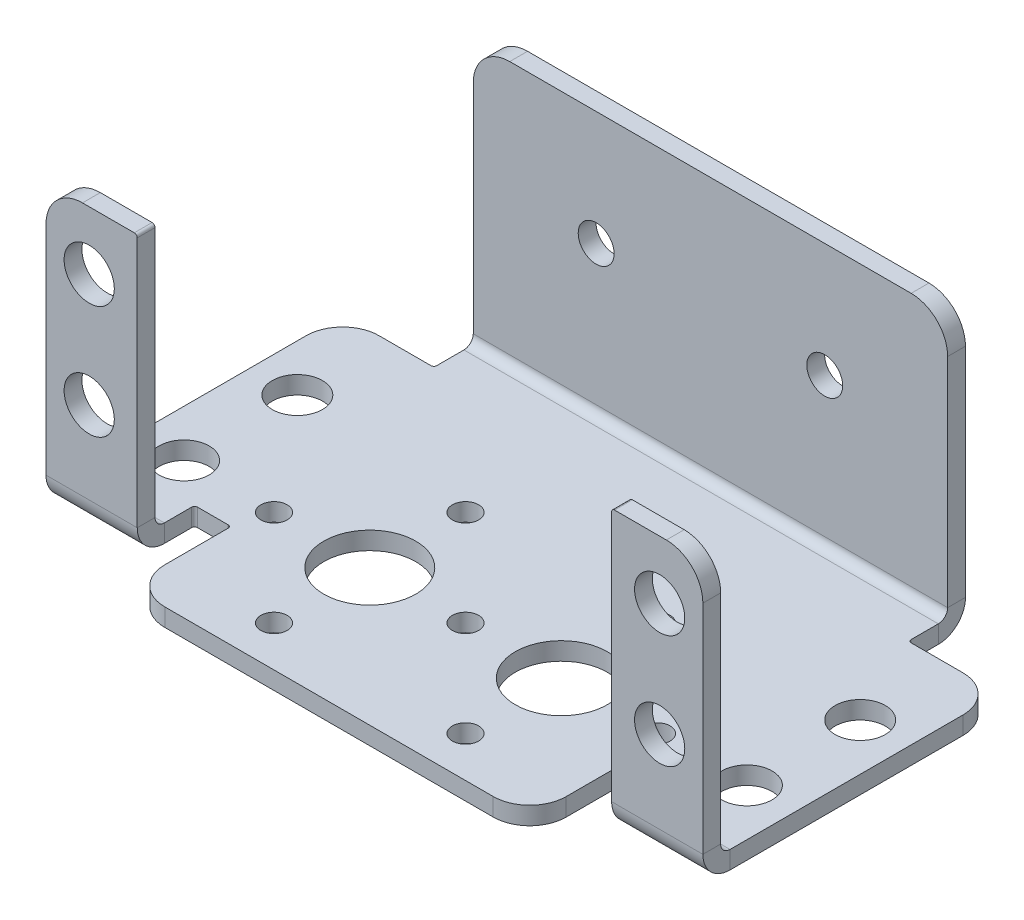
SolidWorks part; units mm, degrees
note: The reader was unsure of these and kept them because the rebuilt part matched: flange length of "Edge-Flange1", "Edge-Flange2".
material "5052-H32"
ref_plane "Front Plane" through (0, 0, 0) normal (0, 0, 1) x (1, 0, 0)
ref_plane "Top Plane" through (0, 0, 0) normal (0, 1, 0) x (1, 0, 0)
ref_plane "Right Plane" through (0, 0, 0) normal (1, 0, 0) x (0, 0, -1)
sketch "Sketch1" plane through (0, 0, 0) normal (0, 1, 0) x (1, 0, 0)
  line L0 (0, 0) -> (0, -11.8745) construction
  line L1 (0, 0) -> (0, 21.3106) construction
  line L2 (-17.4625, -11.8745) -> (17.4625, -11.8745)
  line L3 (17.4625, -11.8745) -> (17.4625, -2.9337)
  line L4 (-17.4625, -11.8745) -> (-17.4625, -2.9337)
  line L5 (17.4625, -2.9337) -> (20.6375, -2.9337)
  line L6 (-17.4625, -2.9337) -> (-20.6375, -2.9337)
  line L7 (20.6375, -2.9337) -> (20.6375, -6.3754)
  line L8 (-20.6375, -2.9337) -> (-20.6375, -6.3754)
  line L9 (20.6375, -6.3754) -> (28.575, -6.3754)
  line L10 (-20.6375, -6.3754) -> (-28.575, -6.3754)
  line L11 (-28.575, -6.3754) -> (-28.575, 17.8816)
  line L12 (28.575, -6.3754) -> (28.575, 17.8816)
  line L13 (-28.575, 17.8816) -> (-20.6375, 17.8816)
  line L14 (28.575, 17.8816) -> (20.6375, 17.8816)
  line L15 (-20.6375, 21.3106) -> (20.6375, 21.3106)
  line L16 (-20.6375, 17.8816) -> (-20.6375, 21.3106)
  line L17 (20.6375, 17.8816) -> (20.6375, 21.3106)
  dimension "D1" = 11.8745
  dimension "D2" = 21.3106
  dimension "D3" = 34.925
  dimension "D4" = 8.9408
  dimension "D5" = 41.275
  dimension "D6" = 7.9375
  dimension "D7" = 7.9375
  dimension "D8" = 3.429
  dimension "D9" = 24.257
sheet metal parameters "Sheet-Metal1" thickness 1.5494 parameters "D1"=0.8128
base flange "Base-Flange1" sketch "Sketch1" thickness 1.5494 reverse thickness direction yes parameters "D1"=0.8128
edge flange "Edge-Flange1" sketch "Sketch5" flange angle 90 flange length 24.4602 flange position material outside bend radius 0.8128 thickness 1.5494 relief rectangular parameters "D6"=10
sketch "Sketch5" plane through (0, 1.5494, -21.3106) normal (0, 0, -1) x (-1, 0, 0)
  line L0 (-20.6375, 0) -> (20.6375, 0) construction
  line L1 (-20.6375, 0) -> (20.6375, 0)
  line L2 (-20.6375, 0) -> (-20.6375, 22.9108)
  line L3 (-20.6375, 22.9108) -> (20.6375, 22.9108)
  line L4 (20.6375, 22.9108) -> (20.6375, 0)
bend "EdgeBend1" bend radius 0.8128 bend angle 90 parameters "D5"=1
edge flange "Edge-Flange2" sketch "Sketch10" flange profiles "Sketch10", "Sketch11" flange angle 90 flange length 24.4602 flange position material outside bend radius 0.8128 thickness 1.5494 relief rectangular parameters "D6"=10, "D8"=0.508
sketch "Sketch10" plane through (0, 1.5494, 6.3754) normal (0, 0, 1) x (1, 0, 0)
  line L2 (-28.575, 0) -> (-28.575, 22.9108)
  line L3 (-28.575, 22.9108) -> (-20.6375, 22.9108)
  line L4 (-20.6375, 22.9108) -> (-20.6375, 0)
  line L5 (-28.575, 0) -> (-20.6375, 0) construction
  line L6 (-28.575, 0) -> (-20.6375, 0)
sketch "Sketch11" plane through (0, 1.5494, 6.3754) normal (0, 0, 1) x (1, 0, 0)
  line L0 (20.6375, 0) -> (28.575, 0) construction
  line L1 (20.6375, 0) -> (28.575, 0)
  line L2 (20.6375, 0) -> (20.6375, 22.9108)
  line L3 (20.6375, 22.9108) -> (28.575, 22.9108)
  line L4 (28.575, 22.9108) -> (28.575, 0)
bend "EdgeBend2" bend radius 0.8128 bend angle 90 parameters "D5"=2
bend "EdgeBend3" bend radius 0.8128 bend angle 90 parameters "D5"=3
sketch "Sketch13" plane through (0, 1.5494, 0) normal (0, 1, 0) x (1, 0, 0)
  line L0 (0, 0) -> (8.3312, 0) construction
  line L1 (8.3312, 0) -> (16.6624, 0) construction
  line L2 (0, 0) -> (-8.3312, 0) construction
  line L3 (-8.3312, 0) -> (-16.6624, 0) construction
  line L4 (8.3312, 0) -> (8.3312, 8.3312) construction
  line L5 (-8.3312, 0) -> (-8.3312, 8.3312) construction
  line L6 (8.3312, 0) -> (8.3312, -8.3312) construction
  line L7 (-8.3312, 0) -> (-8.3312, -8.3312) construction
  line L8 (-16.6624, 0) -> (-24.4856, 0) construction
  line L9 (8.3312, -9.4742) -> (8.3312, -11.8745) construction
  line L10 (-24.4856, 9.8552) -> (-24.4856, 0) construction
  line L11 (16.6624, 0) -> (24.4856, 0) construction
  line L12 (-17.4625, -11.8745) -> (17.4625, -11.8745) construction
  line L13 (24.4856, 9.8552) -> (24.4856, 0) construction
  line L14 (26.67, 0) -> (28.575, 0) construction
  line L15 (28.575, -5.5626) -> (28.575, 17.8816) construction
  circle A0 centre (0, 0) radius 1.143
  circle A1 centre (8.3312, 8.3312) radius 1.143
  circle A2 centre (8.3312, -8.3312) radius 1.143
  circle A3 centre (16.6624, 0) radius 1.143
  circle A4 centre (-8.3312, 8.3312) radius 1.143
  circle A5 centre (-8.3312, -8.3312) radius 1.143
  circle A6 centre (-16.6624, 0) radius 1.143
  circle A7 centre (-8.3312, 0) radius 4.0005
  circle A8 centre (8.3312, 0) radius 4.0005
  circle A9 centre (-24.4856, 9.8552) radius 2.1844
  circle A10 centre (-24.4856, 0) radius 2.1844
  circle A11 centre (24.4856, 9.8552) radius 2.1844
  circle A12 centre (24.4856, 0) radius 2.1844
  dimension "D2" = 2.286
  dimension "D3" = 8.001
  dimension "D6" = 4.3688
  dimension "D1" = 8.3312
  dimension "D4" = 7.8232
  dimension "D5" = 9.8552
extrude "Extrude2" cut sketch "Sketch13" against normal blind 1.5494
sketch "Sketch14" plane through (0, 0, 7.9248) normal (0, 0, 1) x (1, 0, 0)
  line L0 (0, 0) -> (0, 19.3802) construction
  line L1 (-24.8158, 21.5646) -> (-24.8158, 24.4602) construction
  line L2 (-24.8158, 19.3802) -> (-24.8158, 9.525) construction
  line L3 (0, 19.3802) -> (0, 24.4602) construction
  line L4 (-20.6375, 24.4602) -> (-28.575, 24.4602) construction
  line L5 (24.8158, 19.3802) -> (24.8158, 9.525) construction
  line L6 (-20.6375, 24.4602) -> (20.6375, 24.4602) construction
  line L7 (-24.8158, 19.3802) -> (24.8158, 19.3802) construction
  circle A0 centre (-24.8158, 19.3802) radius 2.1844
  circle A1 centre (-24.8158, 9.525) radius 2.1844
  circle A2 centre (24.8158, 19.3802) radius 2.1844
  circle A3 centre (24.8158, 9.525) radius 2.1844
  dimension "D3" = 4.3688
  dimension "D1" = 49.6316
  dimension "D2" = 9.8552
  dimension "D4" = 5.08
extrude "Extrude3" cut sketch "Sketch14" against normal blind 1.5494
sketch "Sketch15" plane through (0, 0, -22.86) normal (0, 0, -1) x (-1, 0, 0)
  line L0 (0, 0) -> (0, 14.5161) construction
  line L1 (0, 24.4602) -> (0, 14.5161) construction
  line L2 (20.6375, 24.4602) -> (-20.6375, 24.4602) construction
  line L3 (-9.9441, 14.5161) -> (9.9441, 14.5161) construction
  circle A0 centre (-9.9441, 14.5161) radius 1.5621
  circle A1 centre (9.9441, 14.5161) radius 1.5621
  dimension "D3" = 3.1242
  dimension "D1" = 9.9441
  dimension "D2" = 19.8882
extrude "Extrude4" cut sketch "Sketch15" against normal blind 1.5494
fillet "Fillet1" radius 3.175 8 edges at (-28.575, 0.7747, -17.8816) (28.575, 0.7747, -17.8816) (17.4625, 0.7747, 11.8745) (-17.4625, 0.7747, 11.8745) (-28.575, 24.4602, 7.1501) (28.575, 24.4602, 7.1501) (20.6375, 24.4602, -22.0853) (-20.6375, 24.4602, -22.0853)
fillet "Fillet2" radius 0.254 8 edges at (20.6375, 0.7747, -17.8816) (-20.6375, 0.7747, -17.8816) (-20.6375, 24.4602, 7.1501) (20.6375, 24.4602, 7.1501) (17.4625, 0.7747, 2.9337) (20.6375, 0.7747, 2.9337) (-20.6375, 0.7747, 2.9337) (-17.4625, 0.7747, 2.9337)
flat pattern "Flat-Pattern1" [suppressed]
sketch "Bend-Lines1" plane through (0, 0, 0) normal (0, 1, 0) x (-1, 0, 0)
bend of the flat pattern "Flatten-<EdgeBend1>1"
bend of the flat pattern "Flatten-<EdgeBend2>1"
bend of the flat pattern "Flatten-<EdgeBend3>1"
